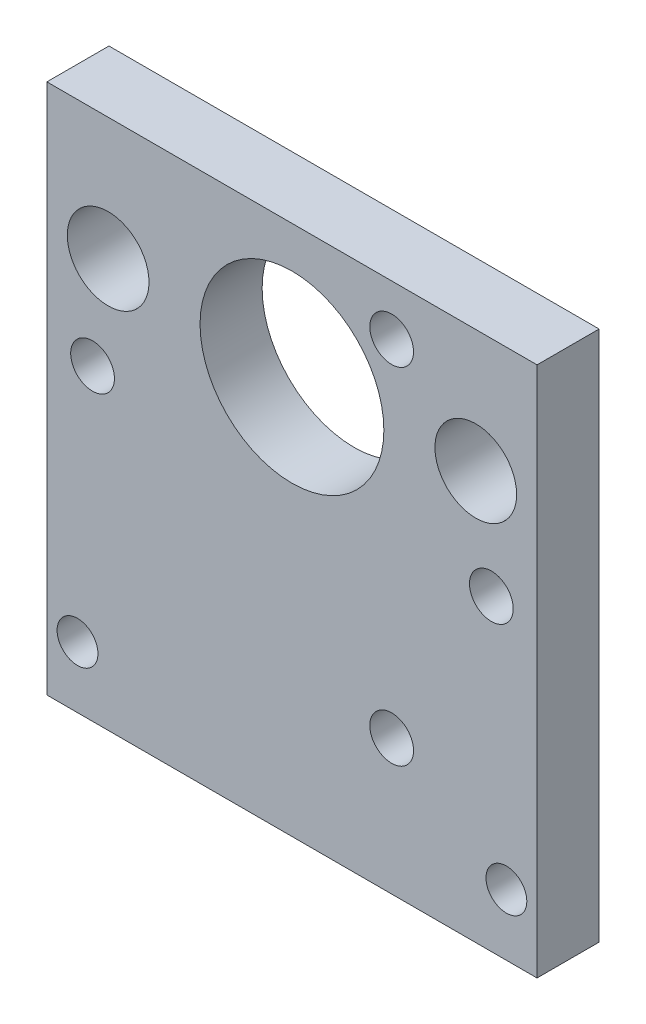
SolidWorks part; units mm, degrees
material "6063-O"
ref_plane "Front" through (0, 0, 0) normal (0, 0, 1) x (1, 0, 0)
ref_plane "Top" through (0, 0, 0) normal (0, 1, 0) x (1, 0, 0)
ref_plane "Right" through (0, 0, 0) normal (1, 0, 0) x (0, 0, -1)
sketch "Sketch1" plane through (0, 0, 0) normal (0, 0, 1) x (1, 0, 0)
  line L1 (19.05, -20.6375) -> (-19.05, -20.6375)
  line L2 (19.05, -20.6375) -> (19.05, 20.6375)
  line L3 (19.05, 20.6375) -> (-19.05, 20.6375)
  line L4 (-19.05, -20.6375) -> (-19.05, 20.6375)
  line L5 (19.05, -20.6375) -> (-19.05, 20.6375) construction
  line L6 (19.05, 20.6375) -> (-19.05, -20.6375) construction
  point P0 (0, 0)
  dimension "D1" = 38.1
  dimension "D2" = 41.275
extrude "Boss-Extrude1" add sketch "Sketch1" along normal blind 4.826
sketch "Sketch2" plane through (0, 0, 4.826) normal (0, 0, 1) x (1, 0, 0)
  line L0 (19.05, 20.6375) -> (-19.05, 20.6375) construction
  line L1 (0, 0) -> (0, 18.787) construction
  line L2 (-15.5, 3.287) -> (15.5, 3.287) construction
  line L3 (7.75, -10.1364) -> (0, 3.287) construction
  line L4 (0, 3.287) -> (7.75, 16.7104) construction
  line L5 (-14.2875, 11.1125) -> (14.2875, 11.1125) construction
  line L6 (-19.05, 20.6375) -> (-19.05, -20.6375) construction
  circle A0 centre (0, 10.287) radius 7.1438
  circle A1 centre (0, 3.287) radius 15.5 construction
  circle A4 centre (7.75, 16.7104) radius 1.7
  circle A5 centre (7.75, -10.1364) radius 1.7
  circle A6 centre (-15.5, 3.287) radius 1.7
  circle A7 centre (15.5, 3.287) radius 1.7
  circle A8 centre (-14.2875, 11.1125) radius 3.175
  circle A9 centre (14.2875, 11.1125) radius 3.175
  point P23 (0, 11.1125)
  dimension "D2" = 14.2875
  dimension "D3" = 31
  dimension "D5" = 3.4
  dimension "D10" = 6.35
  dimension "D1" = 10.3505
  dimension "D4" = 7
  dimension "D6" = 120
  dimension "D7" = 30
  dimension "D8" = 9.525
  dimension "D9" = 4.7625
extrude "Cut-Extrude1" cut sketch "Sketch2" against normal through all contours A0 region at (0, 10.287, 4.826)
hole_wizard "Ø3.4 (3.4) Diameter Hole1" positions "Sketch3" profile "Sketch4" hole size "Ø3.4" standard "ANSI Metric" end condition through all
sketch "Sketch3" plane through (0, 0, 4.826) normal (0, 0, 1) x (1, 0, 0)
  point P0 (-15.5, 3.287)
  point P3 (7.75, 16.7104)
  point P6 (15.5, 3.287)
  point P9 (7.75, -10.1364)
sketch "Sketch4" plane through (-15.5, 3.287, 4.826) normal (1, 0, 0) x (0, -1, 0)
  line L0 (0, 0) -> (0, 4.826)
  line L1 (0, 4.826) -> (1.7, 4.826)
  line L2 (1.7, 4.826) -> (1.7, 0)
  line L5 (1.7, 0) -> (0, 0)
  line L11 (0, -6.35) -> (0, 107.95) construction
  dimension "Thru Hole Dia." = 3.4
  dimension "Thru Hole Depth" = 4.826
hole_wizard "1/4 (0.25) Diameter Hole1" positions "Sketch5" profile "Sketch6" hole size "1/4" standard "ANSI Inch" end condition through all
sketch "Sketch5" plane through (0, 0, 4.826) normal (0, 0, 1) x (1, 0, 0)
  point P0 (-14.2875, 11.1125)
  point P3 (14.2875, 11.1125)
sketch "Sketch6" plane through (-14.2875, 11.1125, 4.826) normal (1, 0, 0) x (0, -1, 0)
  line L0 (0, 0) -> (0, 4.826)
  line L1 (0, 4.826) -> (3.175, 4.826)
  line L2 (3.175, 4.826) -> (3.175, 0)
  line L5 (3.175, 0) -> (0, 0)
  line L11 (0, -6.35) -> (0, 107.95) construction
  dimension "Thru Hole Dia." = 6.35
  dimension "Thru Hole Depth" = 4.826
sketch "Sketch7" plane through (0, 0, 4.826) normal (0, 0, 1) x (1, 0, 0)
  line L0 (-16.6687, -15.875) -> (16.6688, -15.875) construction
  line L3 (-19.05, -20.6375) -> (19.05, -20.6375) construction
  line L4 (0, 0) -> (0, -15.875) construction
  circle A0 centre (-16.6687, -15.875) radius 1.5875
  circle A1 centre (16.6688, -15.875) radius 1.5875
  dimension "D1" = 3.175
  dimension "D2" = 4.7625
  dimension "D3" = 33.3375
hole_wizard "1/8 (0.125) Clearance Dowel Hole1" positions "Sketch10" profile "Sketch11" hole size "1/8" standard "ANSI Inch" end condition through all
sketch "Sketch10" plane through (0, 0, 4.826) normal (0, 0, 1) x (1, 0, 0)
  point P0 (-16.6687, -15.875)
  point P3 (16.6688, -15.875)
sketch "Sketch11" plane through (-16.6687, -15.875, 4.826) normal (1, 0, 0) x (0, -1, 0)
  line L0 (0, 0) -> (0, 4.826)
  line L1 (0, 4.826) -> (1.5875, 4.826)
  line L2 (1.5875, 4.826) -> (1.5875, 0)
  line L5 (1.5875, 0) -> (0, 0)
  line L11 (0, -6.35) -> (0, 107.95) construction
  dimension "Thru Hole Dia." = 3.175
  dimension "Thru Hole Depth" = 4.826
